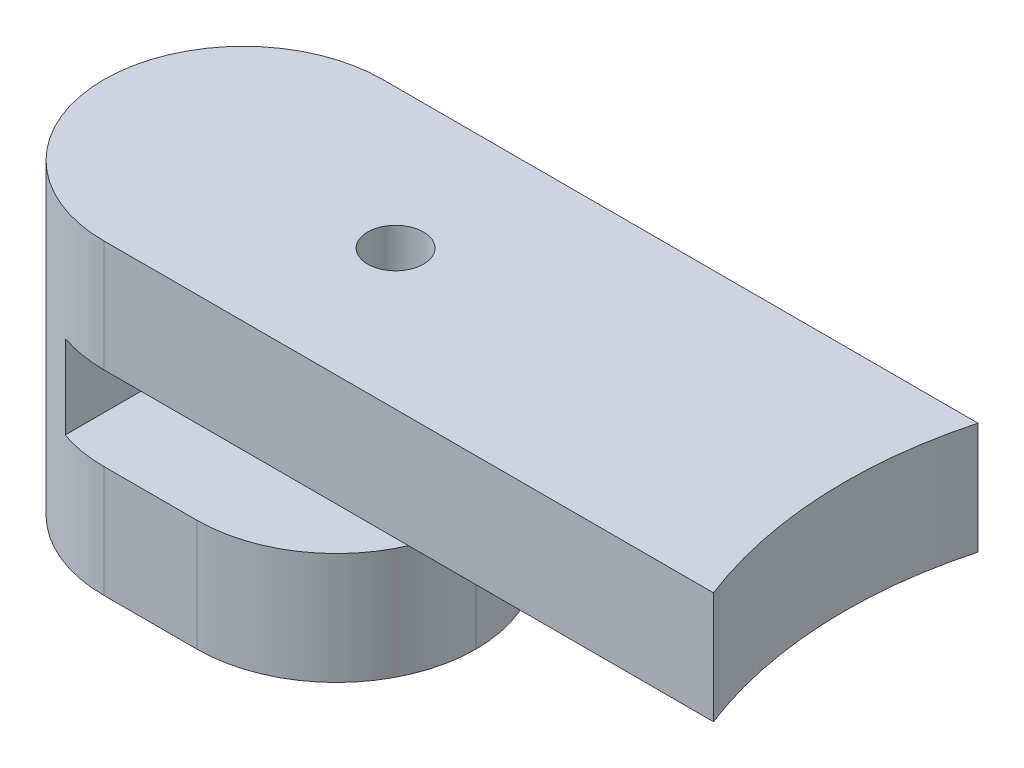
SolidWorks part; units mm, degrees
ref_plane "Front Plane" through (0, 0, 0) normal (0, 0, 1) x (1, 0, 0)
ref_plane "Top Plane" through (0, 0, 0) normal (0, 1, 0) x (1, 0, 0)
ref_plane "Right Plane" through (0, 0, 0) normal (1, 0, 0) x (0, 0, -1)
sketch "Sketch1" plane through (0, 0, 0) normal (0, 1, 0) x (1, 0, 0)
  line L0 (11.75, 3.75) -> (11.75, -3.75)
  line L1 (0, 3.75) -> (11.75, 3.75)
  line L2 (0, 3.75) -> (0, -3.75)
  line L3 (0, -3.75) -> (11.75, -3.75)
  line L4 (11.75, 3.75) -> (11.75, -3.75)
  line L5 (0, 3.75) -> (11.75, -3.75) construction
  line L6 (0, -3.75) -> (11.75, 3.75) construction
  line L7 (11.75, -3.75) -> (4.0932, -3.75)
  line L8 (11.75, 3.75) -> (18.3962, 3.75)
  line L9 (11.75, -3.75) -> (18.3962, -3.75)
  line L10 (18.3962, 3.75) -> (18.3962, -3.75)
  point P0 (0, 0)
extrude "Boss-Extrude1" add sketch "Sketch1" along normal blind 3 contours L1 L2 L3 | L10 L8 L0 L9 region at (15.0731, 0, 0) region at (5.875, 0, 0)
sketch "Sketch3" plane through (0, 3, 0) normal (0, 1, 0) x (1, 0, 0)
  line L0 (0, 3.75) -> (0, -3.75)
  line L5 (0, 3.75) -> (-7.8374, 3.75)
  line L6 (0, -3.75) -> (-7.8374, -3.75)
  line L7 (-7.8374, 3.75) -> (-7.8374, -3.75)
sketch "Sketch2" plane through (0, 3, 0) normal (0, 1, 0) x (1, 0, 0)
  line L0 (0, 3.75) -> (0, -3.75) construction
  circle A0 centre (0, 0) radius 0.75
extrude "Boss-Extrude2" add sketch "Sketch3" against normal up to surface (3 mm away) up to face at (9.1981, 0, 0)
sketch "Sketch4" plane through (0, 3, 0) normal (0, 1, 0) x (1, 0, 0)
  circle A0 centre (23.4764, 0.597) radius 12
  point P2 (24.9473, 0.5056)
  point P3 (23.4764, 0.597)
extrude "Cut-Extrude2" cut sketch "Sketch4" against normal up to surface (3 mm away) up to face at (5.2794, 0, 0)
sketch "Sketch6" plane through (0, 0, 0) normal (0, -1, 0) x (1, 0, 0)
  line L0 (-7.8374, -3.75) -> (11.898, -3.75) construction
  line L1 (-7.8374, 3.75) -> (-5.3374, 3.75)
  line L2 (-7.8374, 3.75) -> (-7.8374, -3.75)
  line L3 (-7.8374, -3.75) -> (-5.3374, -3.75)
  line L4 (-5.3374, 3.75) -> (-5.3374, -3.75)
extrude "Boss-Extrude3" add sketch "Sketch6" along normal blind 5.25
sketch "Sketch7" plane through (-5.3374, 0, 0) normal (1, 0, 0) x (0, 0, -1)
  line L0 (3.75, -5.25) -> (3.75, 0) construction
  line L1 (-3.75, -5.25) -> (3.75, -5.25)
  line L2 (-3.75, -5.25) -> (-3.75, -2.25)
  line L3 (-3.75, -2.25) -> (3.75, -2.25)
  line L4 (3.75, -5.25) -> (3.75, -2.25)
extrude "Boss-Extrude4" add sketch "Sketch7" along normal blind 7.5
extrude "Cut-Extrude1" cut sketch "Sketch2" against normal up to surface (8.25 mm away) up to face at (-2.8374, -5.25, 0)
fillet "Fillet1" radius 3.75 4 edges at (2.1626, -3.75, -3.75) (2.1626, -3.75, 3.75) (-7.8374, -1.125, 3.75) (-7.8374, -1.125, -3.75)
